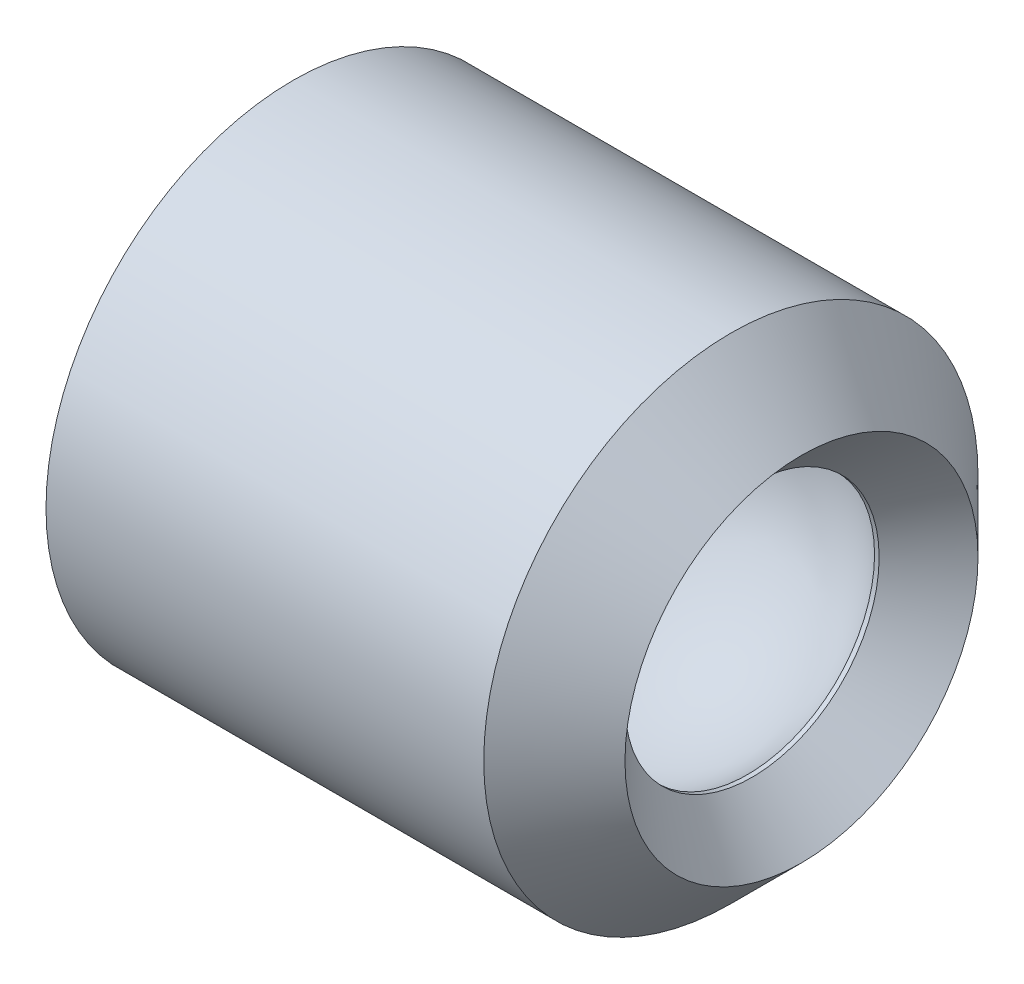
SolidWorks part; units mm, degrees
ref_plane "Płaszczyzna przednia" through (0, 0, 0) normal (0, 0, 1) x (1, 0, 0)
ref_plane "Płaszczyzna górna" through (0, 0, 0) normal (0, 1, 0) x (1, 0, 0)
ref_plane "Płaszczyzna prawa" through (0, 0, 0) normal (1, 0, 0) x (0, 0, -1)
sketch "Szkic1" plane through (0, 0, 0) normal (1, 0, 0) x (0, 0, -1)
  circle A0 centre (0, 0) radius 17.5
  dimension "D1" = 35
extrude "Dodanie-wyciągnięcie1" add sketch "Szkic1" along normal blind 36
sketch "Szkic2" plane through (0, 0, 0) normal (-1, 0, 0) x (0, 0, 1)
  circle A0 centre (0, 0) radius 6
  dimension "D1" = 12
extrude "Wytnij-wyciągnięcie1" cut sketch "Szkic2" against normal blind 10
thread "Gwint1" pitch 1.5 method extrude profile "Profil gwintu1" start angle 0, offset 0, length 10, pitch 1.5, diameter 12
ref_plane "Płaszczyzna1" through (0, 0, -6) normal (0, -1, 0) x (0, 0, -1)
sketch "Profil gwintu1" plane through (0, 0, -6) normal (0, -1, 0) x (0, 0, -1)
  line L0 (0, 0) -> (0, 1.5) construction
  line L11 (0, 0) -> (0, 1.3125)
  line L12 (0, 1.3125) -> (-0.8119, 0.8437)
  line L13 (-0.8119, 0.8437) -> (-0.8119, 0.4687)
  line L15 (-0.8119, 0.4687) -> (0, 0)
  line L17 (-0.8119, 0.6562) -> (0, 0.6562) construction
  point P2 (0, 0)
  dimension "Pitch" = 1.5
  dimension "Profile_Angle" = 60
  dimension "Profile_Land" = 0.375
  dimension "Profile_Height" = 0.8119
sketch "Szkic6" plane through (0, 0, 0) normal (0, 0, 1) x (1, 0, 0)
  line L0 (0, 0) -> (36, 0) construction
  line L1 (36, -17.5) -> (36, 17.5) construction
  line L2 (36, -17.5) -> (36, 17.5) construction
  line L3 (23.5, 12.5) -> (23.5, -12.5)
  arc A0 (23.5, -12.5) -> (23.5, 12.5) centre (23.5, 0) ccw
  dimension "D1" = 25
chamfer "Sfazowanie1" distance 5 angle 45 1 edges at (36, 0, -17.5)
sketch "Szkic7" plane through (36, 0, 0) normal (1, 0, 0) x (0, 0, -1)
  circle A0 centre (0, 0) radius 9
  dimension "D1" = 18
extrude "Wytnij-wyciągnięcie2" cut sketch "Szkic7" against normal blind 11
chamfer "Sfazowanie3" distance 3.5 angle 45 1 edges at (36, 0, -9)
revolve "Wycięcie-obrót13" cut sketch "Szkic6" angle 360 about L3
